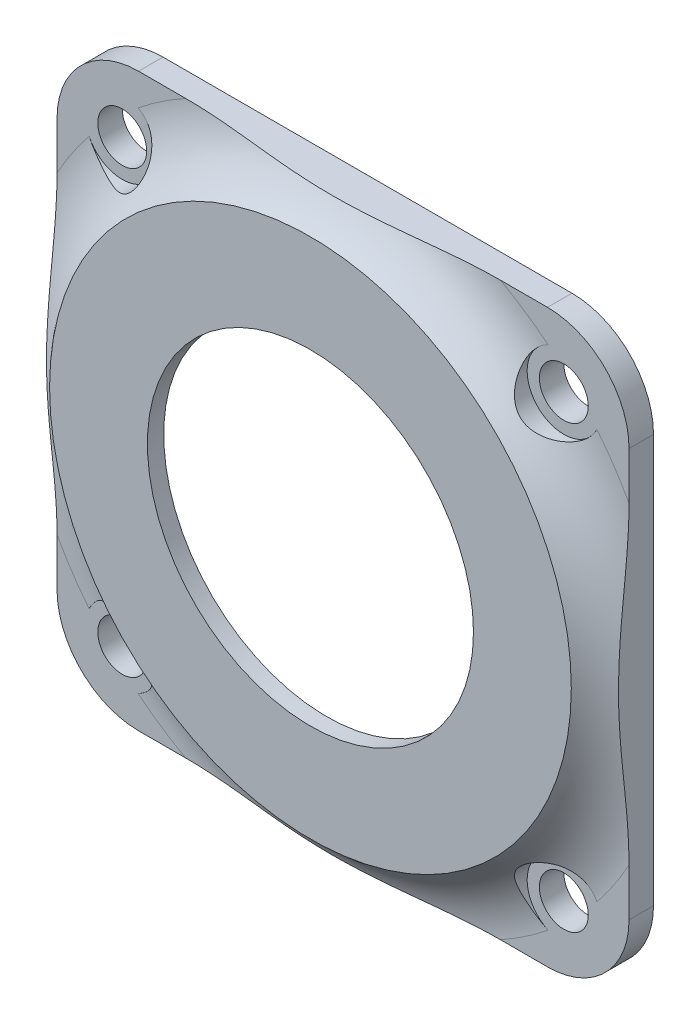
SolidWorks part; units mm, degrees
ref_plane "Alzado" through (0, 0, 0) normal (0, 0, 1) x (1, 0, 0)
ref_plane "Planta" through (0, 0, 0) normal (0, 1, 0) x (1, 0, 0)
ref_plane "Vista lateral" through (0, 0, 0) normal (1, 0, 0) x (0, 0, -1)
sketch "Croquis1" plane through (0, 0, 0) normal (0, 0, 1) x (1, 0, 0)
  line L1 (-35.0823, 35.0342) -> (35.0823, 35.0342)
  line L2 (-35.0823, 35.0342) -> (-35.0823, -35.0342)
  line L3 (-35.0823, -35.0342) -> (35.0823, -35.0342)
  line L4 (35.0823, 35.0342) -> (35.0823, -35.0342)
  line L5 (-35.0823, 35.0342) -> (35.0823, -35.0342) construction
  line L6 (-35.0823, -35.0342) -> (35.0823, 35.0342) construction
  circle A0 centre (0, 0) radius 29
  circle A1 centre (0, 0) radius 35
  dimension "D1" = 58
  dimension "D2" = 70
extrude "Saliente-Extruir1" add sketch "Croquis1" along normal blind 3 contours A1 A0 | L4 L1 L2 L3 A1
fillet "Redondeo1" radius 10 4 edges at (35.0823, -35.0342, 1.5) (-35.0823, -35.0342, 1.5) (-35.0823, 35.0342, 1.5) (35.0823, 35.0342, 1.5)
sketch "Croquis2" plane through (0, 0, 0) normal (0, 0, -1) x (-1, 0, 0)
  line L0 (-35.0823, 25.0342) -> (-35.0823, -25.0342) construction
  line L1 (25.0823, -35.0342) -> (-25.0823, -35.0342) construction
  line L2 (25.0823, 35.0342) -> (-25.0823, 35.0342) construction
  line L3 (35.0823, 25.0342) -> (35.0823, -25.0342) construction
  circle A0 centre (-27.0823, 27.0342) radius 3
  circle A1 centre (27.0823, 27.0342) radius 3
  circle A2 centre (-27.0823, -27.0342) radius 3
  circle A3 centre (27.0823, -27.0342) radius 3
  dimension "D9" = 6
  dimension "D10" = 6
  dimension "D11" = 6
  dimension "D12" = 6
  dimension "D1" = 8
  dimension "D2" = 8
  dimension "D3" = 8
  dimension "D4" = 8
  dimension "D5" = 8
  dimension "D6" = 8
  dimension "D7" = 8
  dimension "D8" = 8
extrude "Cortar-Extruir1" cut sketch "Croquis2" against normal blind 10 contours A1 | A0 | A2 | A3
sketch "Croquis3" plane through (0, 0, 3) normal (0, 0, 1) x (1, 0, 0)
  circle A0 centre (0, 0) radius 29
  circle A1 centre (0, 0) radius 32
  dimension "D1" = 3
extrude "Saliente-Extruir2" add sketch "Croquis3" along normal blind 2
sketch "Croquis4" plane through (0, 0, 5) normal (0, 0, 1) x (1, 0, 0)
  circle A0 centre (0, 0) radius 32
  circle A1 centre (0, 0) radius 20
  dimension "D1" = 40
extrude "Saliente-Extruir3" add sketch "Croquis4" along normal blind 2
ref_plane "Plano2" through (0, 0, 7) normal (0, 0, 1) x (1, 0, 0)
sketch "Croquis8" plane through (0, 0, 3) normal (0, 0, 1) x (1, 0, 0)
  circle A0 centre (-27.0823, 27.0342) radius 4.5
  circle A1 centre (27.0823, 27.0342) radius 4.5
  circle A2 centre (27.0823, -27.0342) radius 4.5
  circle A3 centre (-27.0823, -27.0342) radius 4.5
  dimension "D1" = 9
  dimension "D2" = 9
  dimension "D3" = 9
  dimension "D4" = 9
fillet "Redondeo3" radius 10 1 edges at (32, 0, 3)
extrude "Cortar-Extruir3" cut sketch "Croquis8" along normal blind 3
